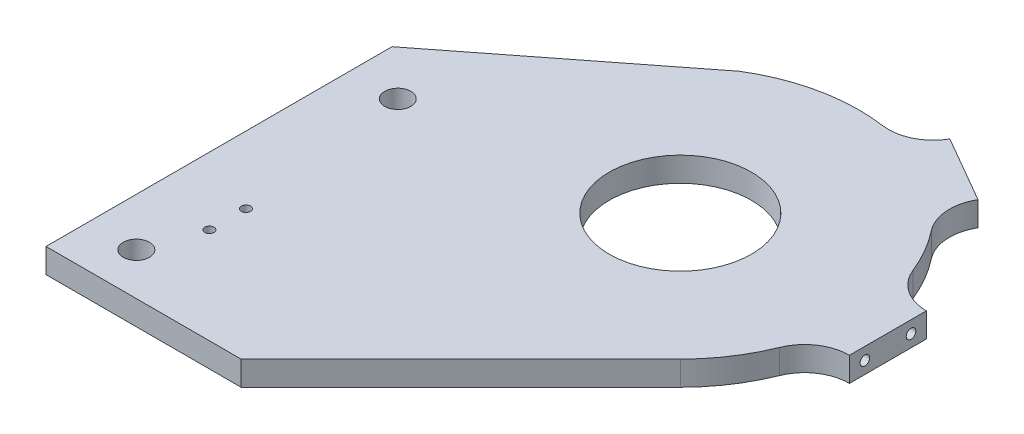
SolidWorks part; units mm, degrees
material "6061 Alloy"
ref_plane "Front Plane" through (0, 0, 0) normal (0, 0, 1) x (1, 0, 0)
ref_plane "Top Plane" through (0, 0, 0) normal (0, 1, 0) x (1, 0, 0)
ref_plane "Right Plane" through (0, 0, 0) normal (1, 0, 0) x (0, 0, -1)
sketch "Sketch2" plane through (0, 0, 0) normal (0, 1, 0) x (1, 0, 0)
  line L0 (50.7609, 129.6827) -> (50.7609, 0) construction
  line L1 (0, 0) -> (50.7609, 0)
  line L2 (0, 0) -> (0, 90)
  line L3 (0, 129.6827) -> (50.7609, 129.6827) construction
  line L6 (107.8805, 57.1195) -> (50.7609, 0)
  line L8 (0, 129.6827) -> (0, 90) construction
  line L9 (0, 90) -> (75, 90) construction
  line L10 (0, 90) -> (50.7609, 129.6827)
  arc A1 (50.7609, 129.6827) -> (107.8805, 57.1195) centre (75, 90) cw
  dimension "D1" = 90
  dimension "D3" = 46.5
  dimension "D2" = 75
  dimension "D5" = 45
base flange "Base-Flange1" sketch "Sketch2" thickness 6.35 reverse thickness direction no parameters "D1"=0.7366
sketch "Sketch8" plane through (0, 0, 0) normal (0, 1, 0) x (1, 0, 0)
  line L1 (0, 90) -> (0, 0) construction
  line L2 (0, 45) -> (79.3207, 45) construction
  line L3 (0, 90) -> (121.5, 90) construction
  line L4 (79.3207, 28.5598) -> (79.3207, 90) construction
  line L5 (50.7609, 0) -> (107.8805, 57.1195) construction
  line L6 (0, 90) -> (0, 0) construction
  circle A1 centre (12.5, 79) radius 3.4
  circle A3 centre (12.5, 11) radius 3.4
  arc A4 (107.8805, 57.1195) -> (50.7609, 129.6827) centre (75, 90) ccw construction
  dimension "D1" = 6.8
  dimension "D3" = 12.5
  dimension "D2" = 11
extrude "Cut-Extrude1" cut sketch "Sketch8" against normal through all normal cut yes
sketch "Sketch9" plane through (0, 0, 0) normal (0, 1, 0) x (1, 0, 0)
  arc A0 (107.8805, 57.1195) -> (50.7609, 129.6827) centre (75, 90) ccw construction
  arc A1 (107.8805, 57.1195) -> (50.7609, 129.6827) centre (75, 90) ccw construction
  circle A2 centre (75, 90) radius 18.5
  dimension "D1" = 37
extrude "Cut-Extrude2" cut sketch "Sketch9" against normal through all normal cut yes
sketch "Sketch10" plane through (0, 0, 0) normal (0, 1, 0) x (1, 0, 0)
  circle A0 centre (75, 111.25) radius 1.5
  circle A1 centre (75, 68.75) radius 1.5
  circle A2 centre (75, 90) radius 18.5 construction
  circle A3 centre (75, 90) radius 18.5 construction
  circle A4 centre (75, 90) radius 21.25 construction
  dimension "D1" = 3
  dimension "D2" = 3
  dimension "D3" = 42.5
extrude "Cut-Extrude3" [suppressed] cut sketch "Sketch10" against normal through all
sketch "Sketch11" plane through (0, 0, 0) normal (0, 1, 0) x (1, 0, 0)
  line L0 (28.5, 90) -> (28.5, 112.2801) construction
  line L1 (50.7609, 129.6827) -> (0, 90) construction
  line L2 (17.5, 34.5) -> (17.5, 25) construction
  line L3 (28.5, 90) -> (0, 90) construction
  line L4 (0, 0) -> (50.7609, 0) construction
  circle A0 centre (75, 90) radius 18.5 construction
  circle A1 centre (75, 90) radius 18.5 construction
  circle A2 centre (75, 90) radius 46.5 construction
  circle A3 centre (17.5, 25) radius 1.2
  circle A4 centre (17.5, 34.5) radius 1.2
  dimension "D1" = 93
  dimension "D2" = 2.4
  dimension "D3" = 9.5
  dimension "D5" = 25
  dimension "D4" = 11
extrude "Cut-Extrude4" cut sketch "Sketch11" against normal through all normal cut yes
sketch "Sketch15" plane through (0, -6.35, 0) normal (0, -1, 0) x (1, 0, 0)
  line L0 (75, -90) -> (129, -90) construction
  line L1 (129, -100) -> (129, -80)
  line L2 (129, -80) -> (120.412, -80) construction
  arc A0 (50.7609, -129.6827) -> (107.8805, -57.1195) centre (75, -90) ccw construction
  arc A1 (50.7609, -129.6827) -> (107.8805, -57.1195) centre (75, -90) ccw construction
  arc A2 (129, -80) -> (118.1479, -72.6648) centre (129, -68.3048) cw
  arc A3 (129, -100) -> (118.1479, -107.3352) centre (129, -111.6952) ccw
  arc A4 (118.1479, -72.6648) -> (118.1479, -107.3352) centre (75, -90) cw
  point P3 (121.5, -90)
  dimension "D1" = 7.5
  dimension "D2" = 20
extrude "Boss-Extrude2" add sketch "Sketch15" against normal up to surface (6.35 mm away) up to face at (17.5, 0, -23.8)
sketch "Sketch16" plane through (129, 0, 0) normal (1, 0, 0) x (0, 0, -1)
  line L0 (90, 0) -> (90, -6.35) construction
  line L1 (80, 0) -> (100, 0) construction
  line L2 (100, 0) -> (100, -6.35) construction
  point P5 (96, -3.175)
  point P9 (100, -3.175)
  point P12 (84, -3.175)
  dimension "D1" = 4
hole_wizard "Tap Drill for M3x0.5 Tap2" positions "Sketch16" profile "Sketch17" hole size "M3x0.5" standard "ANSI Metric"
sketch "Sketch17" plane through (129, -3.175, -84) normal (0, 1, 0) x (0, 0, -1)
  line L0 (0, 0) -> (0, 5.7511)
  line L1 (0, 5.7511) -> (1.25, 5)
  line L2 (1.25, 5) -> (1.25, 0)
  line L5 (1.25, 0) -> (0, 0)
  line L10 (0, 5.7511) -> (-1.25, 5) construction
  line L11 (0, -6.35) -> (0, 107.95) construction
  dimension "Hole Dia." = 2.5
  dimension "Hole Depth" = 5
  dimension "Drill Angle" = 118
pattern_circular "CirPattern3" count 2 over 60 about axis through (75, 0, -90) along (0, 1, 0) of "Boss-Extrude2", "Tap Drill for M3x0.5 Tap2"
sketch "Bend-Lines1" [suppressed] plane through (0, 0, 0) normal (0, 1, 0) x (1, 0, 0)
sketch "Bounding-Box1" [suppressed] plane through (0, 0, 0) normal (0, 1, 0) x (1, 0, 0)
sheet metal parameters "Sheet-Metal1" thickness 6.35 parameters "D1"=0.7366
flat pattern "Flat-Pattern1" [suppressed]
sketch "Bend-Lines2" plane through (0, 0, 0) normal (0, 1, 0) x (1, 0, 0)
sketch3d "Bounding-Box2" [suppressed]
  line L0 (37.25, -37.25, 0) -> (37.25, 37.25, 0) construction
  line L1 (-22.5, -37.25, 0) -> (-22.5, 37.25, 0) construction
  line L2 (37.25, -37.25, 0) -> (-22.5, -37.25, 0) construction
  line L3 (37.25, 37.25, 0) -> (-22.5, 37.25, 0) construction
sheet metal parameters "Sheet-Metal2" thickness 6.35 parameters "D1"=0.7366
flat pattern "Flat-Pattern1"
sketch "Bend-Lines2" plane through (0, 0, 0) normal (0, 1, 0) x (1, 0, 0)
sketch3d "Bounding-Box2" [suppressed]
  line L0 (-107.7298, -46.3484, 0) -> (0.0689, 64.7304, 0) construction
  line L1 (-42.0452, -110.0934, 0) -> (65.7535, 0.9853, 0) construction
  line L2 (-107.7298, -46.3484, 0) -> (-42.0452, -110.0934, 0) construction
  line L3 (0.0689, 64.7304, 0) -> (65.7535, 0.9853, 0) construction
sheet metal parameters "Sheet-Metal3" thickness 6.35 parameters "D1"=0.7366
flat pattern "Flat-Pattern1"
sketch "Bend-Lines2" plane through (0, 0, 0) normal (0, 1, 0) x (1, 0, 0)
sketch3d "Bounding-Box2" [suppressed]
  line L0 (-120, -45, 0) -> (-4.6195, 70.3805, 0) construction
  line L1 (-49.6195, -115.3805, 0) -> (65.7609, 0, 0) construction
  line L2 (-120, -45, 0) -> (-49.6195, -115.3805, 0) construction
  line L3 (-4.6195, 70.3805, 0) -> (65.7609, 0, 0) construction
sheet metal parameters "Sheet-Metal4" thickness 6.35 parameters "D1"=0.7366
flat pattern "Flat-Pattern1"
sketch "Bend-Lines2" plane through (0, 0, 0) normal (0, 1, 0) x (1, 0, 0)
sketch3d "Bounding-Box2" [suppressed]
  line L0 (-120, -45, 0) -> (-4.6195, 70.3805, 0) construction
  line L1 (-49.6195, -115.3805, 0) -> (65.7609, 0, 0) construction
  line L2 (-120, -45, 0) -> (-49.6195, -115.3805, 0) construction
  line L3 (-4.6195, 70.3805, 0) -> (65.7609, 0, 0) construction
sheet metal parameters "Sheet-Metal5" thickness 6.35 parameters "D1"=0.7366
flat pattern "Flat-Pattern1"
sketch "Bend-Lines2" plane through (0, 0, 0) normal (0, 1, 0) x (1, 0, 0)
sketch3d "Bounding-Box2" [suppressed]
  line L0 (-120, -45, 0) -> (-4.6195, 70.3805, 0) construction
  line L1 (-49.6195, -115.3805, 0) -> (65.7609, 0, 0) construction
  line L2 (-120, -45, 0) -> (-49.6195, -115.3805, 0) construction
  line L3 (-4.6195, 70.3805, 0) -> (65.7609, 0, 0) construction
sheet metal parameters "Sheet-Metal9" thickness 6.35 parameters "D1"=0.7366
flat pattern "Flat-Pattern1"
sketch "Bend-Lines2" plane through (0, 0, 0) normal (0, 1, 0) x (1, 0, 0)
sketch3d "Bounding-Box2" [suppressed]
  line L0 (-120, -45, 0) -> (-4.6195, 70.3805, 0) construction
  line L1 (-49.6195, -115.3805, 0) -> (65.7609, 0, 0) construction
  line L2 (-120, -45, 0) -> (-49.6195, -115.3805, 0) construction
  line L3 (-4.6195, 70.3805, 0) -> (65.7609, 0, 0) construction
sheet metal parameters "Sheet-Metal10" thickness 6.35 parameters "D1"=0.7366
flat pattern "Flat-Pattern1"
sketch "Bend-Lines2" plane through (0, 0, 0) normal (0, 1, 0) x (1, 0, 0)
sketch3d "Bounding-Box2" [suppressed]
  line L0 (-120, -45, 0) -> (-4.6195, 70.3805, 0) construction
  line L1 (-49.6195, -115.3805, 0) -> (65.7609, 0, 0) construction
  line L2 (-120, -45, 0) -> (-49.6195, -115.3805, 0) construction
  line L3 (-4.6195, 70.3805, 0) -> (65.7609, 0, 0) construction
sheet metal parameters "Sheet-Metal12" thickness 6.35 parameters "D1"=0.7366
flat pattern "Flat-Pattern1"
sketch "Bend-Lines2" plane through (0, 0, 0) normal (0, 1, 0) x (1, 0, 0)
sketch3d "Bounding-Box2" [suppressed]
  line L0 (-120, -45, 0) -> (1.2128, 76.2128, 0) construction
  line L1 (-49.6195, -115.3805, 0) -> (71.5933, 5.8323, 0) construction
  line L2 (-120, -45, 0) -> (-49.6195, -115.3805, 0) construction
  line L3 (1.2128, 76.2128, 0) -> (71.5933, 5.8323, 0) construction
equation "\"L1L\"=500"
equation "\"L1Thick\"=6.35"
equation "\"Harm-Drive-Outer\"=74.5"
equation "\"L1-Spacing\"=115.65"
equation "\"L-Bracket-HoleToWall\"=12.5"
equation "\"Bracket-Hole-D\"=6.8"
equation "\"D1@Sketch8\"=\"Bracket-Hole-D\""
equation "\"L-Bracket-HoleToSide\"=11"
equation "\"D3@Sketch8\"=\"L-Bracket-HoleToWall\""
equation "\"D2@Sketch8\"=\"L-Bracket-HoleToSide\""
